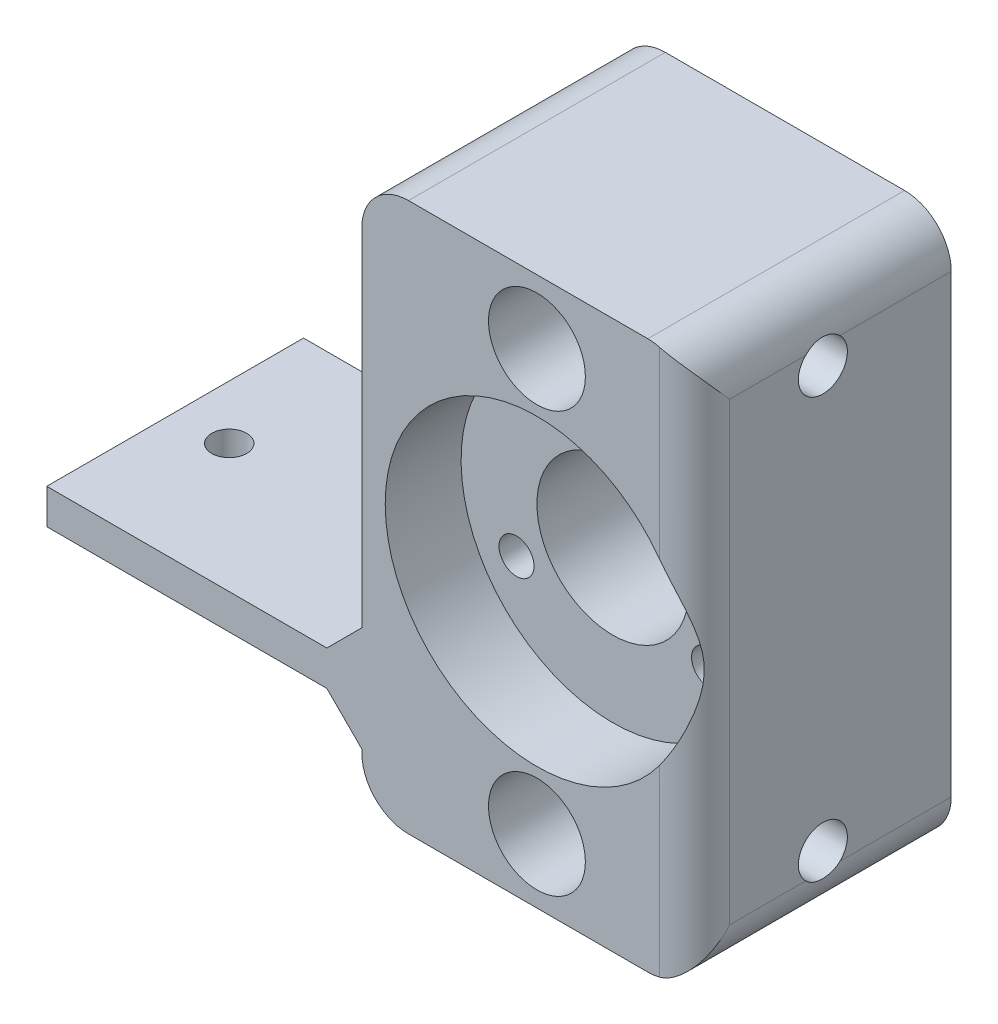
SolidWorks part; units mm, degrees
note: The reader was unsure of these and kept them because the rebuilt part matched: shared geometry of "Sketch1<3>", "Sketch1<4>", "Sketch5<3>".
ref_plane "Front Plane" through (0, 0, 0) normal (0, 0, 1) x (1, 0, 0)
ref_plane "Top Plane" through (0, 0, 0) normal (0, 1, 0) x (1, 0, 0)
ref_plane "Right Plane" through (0, 0, 0) normal (1, 0, 0) x (0, 0, -1)
sketch "Sketch1" plane through (0, 0, 0) normal (0, 0, 1) x (1, 0, 0)
  line L0 (0, 18) -> (0, -18) construction
  line L1 (-15, -23.5) -> (13.5, -23.5)
  line L2 (-15, -23.5) -> (-15, 23.5)
  line L3 (-15, 23.5) -> (13.5, 23.5)
  line L4 (15, -23.5) -> (15, 23.5) construction
  line L5 (-15, -23.5) -> (15, 23.5) construction
  line L6 (-15, 23.5) -> (15, -23.5) construction
  line L7 (13.5, -23.5) -> (13.5, 23.5)
  line L8 (13.5, 23.5) -> (15, 23.5) construction
  line L9 (13.5, -23.5) -> (15, -23.5) construction
  circle A0 centre (0, 18) radius 4.15
  circle A1 centre (0, -18) radius 4.15
  circle A2 centre (0, 18) radius 3.65
  circle A3 centre (0, -18) radius 3.65
  circle A4 centre (0, 0) radius 6.5
  circle A5 centre (0, 0) radius 13
  point P0 (0, 0)
  point P10 (0, 0)
  dimension "D3" = 8.3
  dimension "D5" = 0.5
  dimension "D6" = 13
  dimension "D7" = 26
  dimension "D1" = 47
  dimension "D2" = 30
  dimension "D4" = 36
  dimension "D8" = 1.5
extrude "Boss-Extrude1" add sketch "Sketch1" along normal blind 2 contours L1 L4 L3 L2 A1 A0 | A0 A2 | A2 | A1 A3
extrude "Boss-Extrude2" add sketch "Sketch1<3>" along normal blind 22 contours L1 L4 L3 L2 A1 A0
sketch "Sketch1<3>" plane through (0, 0, 0) normal (0, 0, 1) x (1, 0, 0) same geometry as "Sketch1"
sketch "Sketch2" plane through (-15, 0, 0) normal (-1, 0, 0) x (0, 0, 1)
  line L0 (0, 0) -> (22, 0) construction
  line L1 (0, -23.5) -> (0, 23.5) construction
  line L2 (22, -23.5) -> (22, 23.5) construction
  line L3 (0, -16.2) -> (22, -16.2)
  line L4 (22, -16.2) -> (22, -13.2)
  line L5 (22, -13.2) -> (0, -13.2)
  line L6 (0, -13.2) -> (0, -16.2)
  dimension "D1" = 13.2
  dimension "D2" = 3
extrude "Boss-Extrude3" add sketch "Sketch2" along normal blind 27
extrude "Boss-Extrude4" add sketch "Sketch1<4>" along normal blind 15.5 contours A5 A4
sketch "Sketch1<4>" plane through (0, 0, 0) normal (0, 0, 1) x (1, 0, 0) same geometry as "Sketch1"
sketch "Sketch3" plane through (0, 0, 15.5) normal (0, 0, 1) x (1, 0, 0)
  circle A0 centre (0, 9.525) radius 1.5
  circle A1 centre (8.2489, -4.7625) radius 1.5
  circle A2 centre (-8.2489, -4.7625) radius 1.5
  point P10 (0, 0)
  dimension "D2" = 3
  dimension "D1" = 9.525
  dimension "D3" = 3
extrude "Cut-Extrude1" cut sketch "Sketch3" against normal through all
sketch "Sketch5" plane through (13.5, 0, 0) normal (1, 0, 0) x (0, 0, -1)
  line L1 (-22, 23.5) -> (0, 23.5) construction
  line L4 (-6.9585, 18) -> (-8.9793, 21.5)
  line L5 (-8.9793, 21.5) -> (-13.0207, 21.5)
  line L6 (-13.0207, 21.5) -> (-15.0415, 18)
  line L7 (-15.0415, 18) -> (-13.0207, 14.5)
  line L8 (-13.0207, 14.5) -> (-8.9793, 14.5)
  line L9 (-8.9793, 14.5) -> (-6.9585, 18)
  line L10 (-6.9585, -18) -> (-8.9793, -14.5)
  line L11 (-8.9793, -14.5) -> (-13.0207, -14.5)
  line L12 (-13.0207, -14.5) -> (-15.0415, -18)
  line L13 (-15.0415, -18) -> (-13.0207, -21.5)
  line L14 (-13.0207, -21.5) -> (-8.9793, -21.5)
  line L15 (-8.9793, -21.5) -> (-6.9585, -18)
  circle A0 centre (-11, -18) radius 2.1
  circle A1 centre (-11, 18) radius 2.1
  circle A2 centre (-11, 18) radius 3.5 construction
  circle A3 centre (-11, -18) radius 3.5 construction
  point P6 (-11, 23.5)
  dimension "D1" = 4.2
  dimension "D2" = 7
extrude "Cut-Extrude3" cut sketch "Sketch5" against normal up to next contours A1 | A0
extrude "Cut-Extrude4" cut sketch "Sketch5<3>" against normal up to next from offset 5 offset against normal yes
sketch "Sketch5<3>" plane through (13.5, 0, 0) normal (1, 0, 0) x (0, 0, -1) same geometry as "Sketch5"
sketch "Sketch6" plane through (0, -13.2, 0) normal (0, 1, 0) x (1, 0, 0)
  line L0 (-42, -22) -> (-42, 0) construction
  line L1 (-15, -22) -> (-15, 0) construction
  circle A0 centre (-37.367, -11) radius 1.5
  circle A1 centre (-23.367, -11) radius 1.5
  point P4 (-24.867, -11)
  point P7 (-42, -11)
  point P8 (-35.867, -11)
  point P9 (-35.367, -11)
  dimension "D4" = 3
  dimension "D1" = 11
  dimension "D2" = 0.5
  dimension "D3" = 20.367
extrude "Cut-Extrude5" cut sketch "Sketch6" against normal up to next
chamfer "Chamfer1" distance 3 angle 45 2 edges at (-15, -16.2, 11) (-15, -13.2, 11)
fillet "Fillet1" radius 4 4 edges at (-15, -23.5, 11) (-15, 23.5, 11) (13.5, 23.5, 11) (13.5, -23.5, 11)
fillet "Fillet2" radius 3 1 edges at (13.5, 0, 22)
sketch "Sketch7" plane through (0, 0, 0) normal (0, 0, -1) x (-1, 0, 0)
  line L0 (0, 9.525) -> (0, 0) construction
  line L7 (1.5877, 6.775) -> (3.1754, 9.525)
  line L8 (3.1754, 9.525) -> (1.5877, 12.275)
  line L9 (1.5877, 12.275) -> (-1.5877, 12.275)
  line L10 (-1.5877, 12.275) -> (-3.1754, 9.525)
  line L11 (-3.1754, 9.525) -> (-1.5877, 6.775)
  line L12 (-1.5877, 6.775) -> (1.5877, 6.775)
  line L13 (11.4243, -4.7625) -> (9.8366, -2.0125)
  line L14 (9.8366, -2.0125) -> (6.6612, -2.0125)
  line L15 (6.6612, -2.0125) -> (5.0735, -4.7625)
  line L16 (5.0735, -4.7625) -> (6.6612, -7.5125)
  line L17 (6.6612, -7.5125) -> (9.8366, -7.5125)
  line L18 (9.8366, -7.5125) -> (11.4243, -4.7625)
  line L19 (-9.8366, -7.5125) -> (-6.6612, -7.5125)
  line L20 (-6.6612, -7.5125) -> (-5.0735, -4.7625)
  line L21 (-5.0735, -4.7625) -> (-6.6612, -2.0125)
  line L22 (-6.6612, -2.0125) -> (-9.8366, -2.0125)
  line L23 (-9.8366, -2.0125) -> (-11.4243, -4.7625)
  line L24 (-11.4243, -4.7625) -> (-9.8366, -7.5125)
  circle A0 centre (0, 9.525) radius 1.5 construction
  circle A1 centre (0, 9.525) radius 2.75 construction
  point P5 (0, 6.775)
  point P27 (0, 0)
  dimension "D1" = 5.5
  dimension "D2" = 3
extrude "Cut-Extrude6" cut sketch "Sketch7" against normal blind 4
